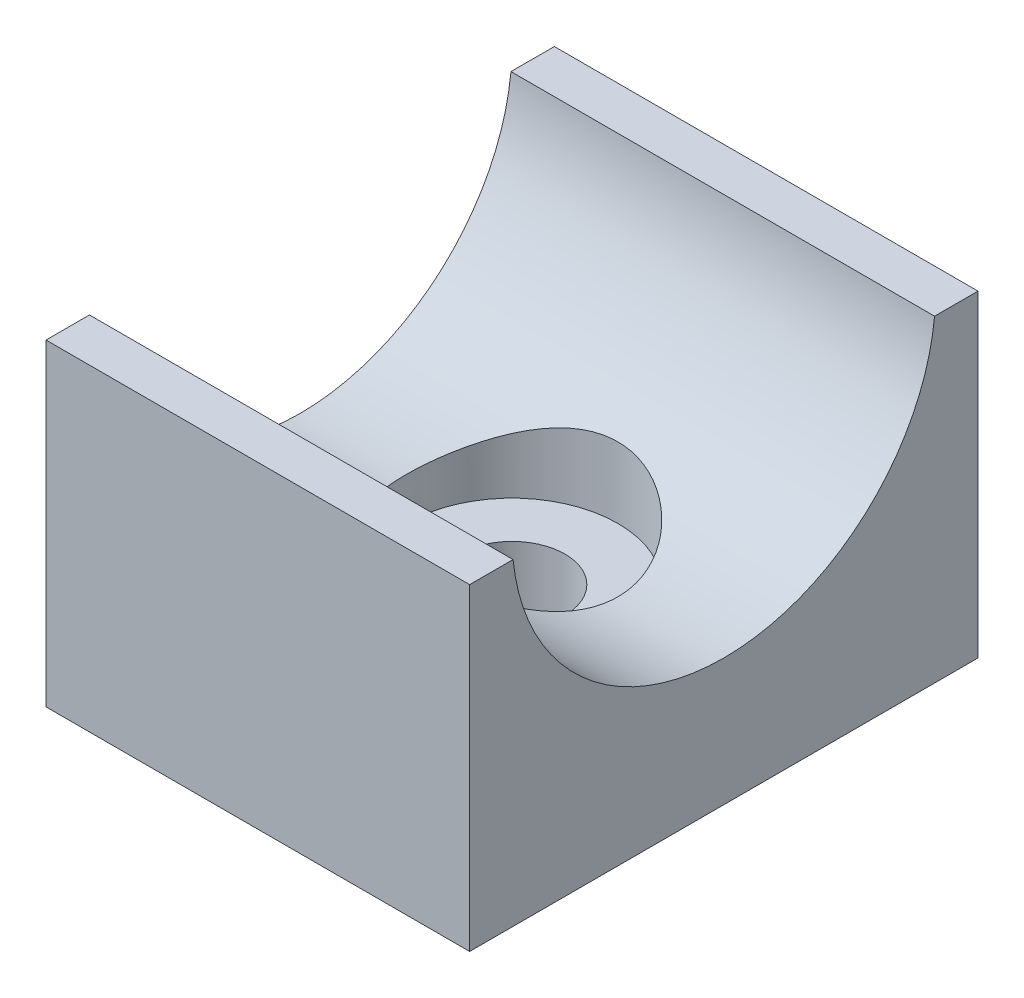
SolidWorks part; units mm, degrees
ref_plane "Front Plane" through (0, 0, 0) normal (0, 0, 1) x (1, 0, 0)
ref_plane "Top Plane" through (0, 0, 0) normal (0, 1, 0) x (1, 0, 0)
ref_plane "Right Plane" through (0, 0, 0) normal (1, 0, 0) x (0, 0, -1)
sketch "Sketch1" plane through (0, 0, 0) normal (1, 0, 0) x (0, 0, -1)
  line L0 (27.8763, 19.05) -> (30.48, 19.05)
  line L1 (0, 0) -> (30.48, 0)
  line L2 (0, 0) -> (0, 19.05)
  line L3 (0, 19.05) -> (2.6037, 19.05)
  line L4 (30.48, 0) -> (30.48, 19.05)
  arc A0 (2.6037, 19.05) -> (27.8763, 19.05) centre (15.24, 20.32) ccw
  point P6 (0, 0)
  dimension "D3" = 12.7
  dimension "D1" = 30.48
  dimension "D2" = 19.05
  dimension "D4" = 1.27
extrude "Boss-Extrude1" add sketch "Sketch1" along normal blind 25.4
sketch "Sketch2" plane through (0, 0, 0) normal (0, -1, 0) x (1, 0, 0)
  line L0 (12.7, 0) -> (12.7, -30.48) construction
  line L1 (25.4, 0) -> (0, 0) construction
  line L2 (25.4, -30.48) -> (0, -30.48) construction
  line L3 (25.4, -15.24) -> (0, -15.24) construction
  line L4 (25.4, 0) -> (25.4, -30.48) construction
  line L5 (0, 0) -> (0, -30.48) construction
  circle A0 centre (12.7, -15.24) radius 3.175
  point P14 (12.7, -15.24)
  dimension "D1" = 6.35
extrude "Cut-Extrude1" cut sketch "Sketch2" against normal through all and the other way through all
ref_plane "Plane1" through (0, 19.05, 0) normal (0, 1, 0) x (1, 0, 0)
sketch "Sketch3" plane through (0, 19.05, 0) normal (0, 1, 0) x (1, 0, 0)
  line L0 (0, 15.24) -> (25.4, 15.24) construction
  line L1 (0, 27.8763) -> (0, 2.6037) construction
  line L2 (25.4, 2.6037) -> (25.4, 27.8763) construction
  line L3 (12.7, 0) -> (12.7, 30.48) construction
  line L4 (25.4, 0) -> (0, 0) construction
  line L5 (25.4, 30.48) -> (0, 30.48) construction
  circle A0 centre (12.7, 15.24) radius 6.35
  point P14 (0, 0)
  point P15 (15.6702, 15.24)
  point P16 (0, 0)
  point P17 (12.7, 15.24)
  dimension "D1" = 12.7
extrude "Cut-Extrude3" cut sketch "Sketch3" against normal offset from surface (13.97 mm away) 5.08 contours A0 up to face at (12.7, 0, -12.065)
